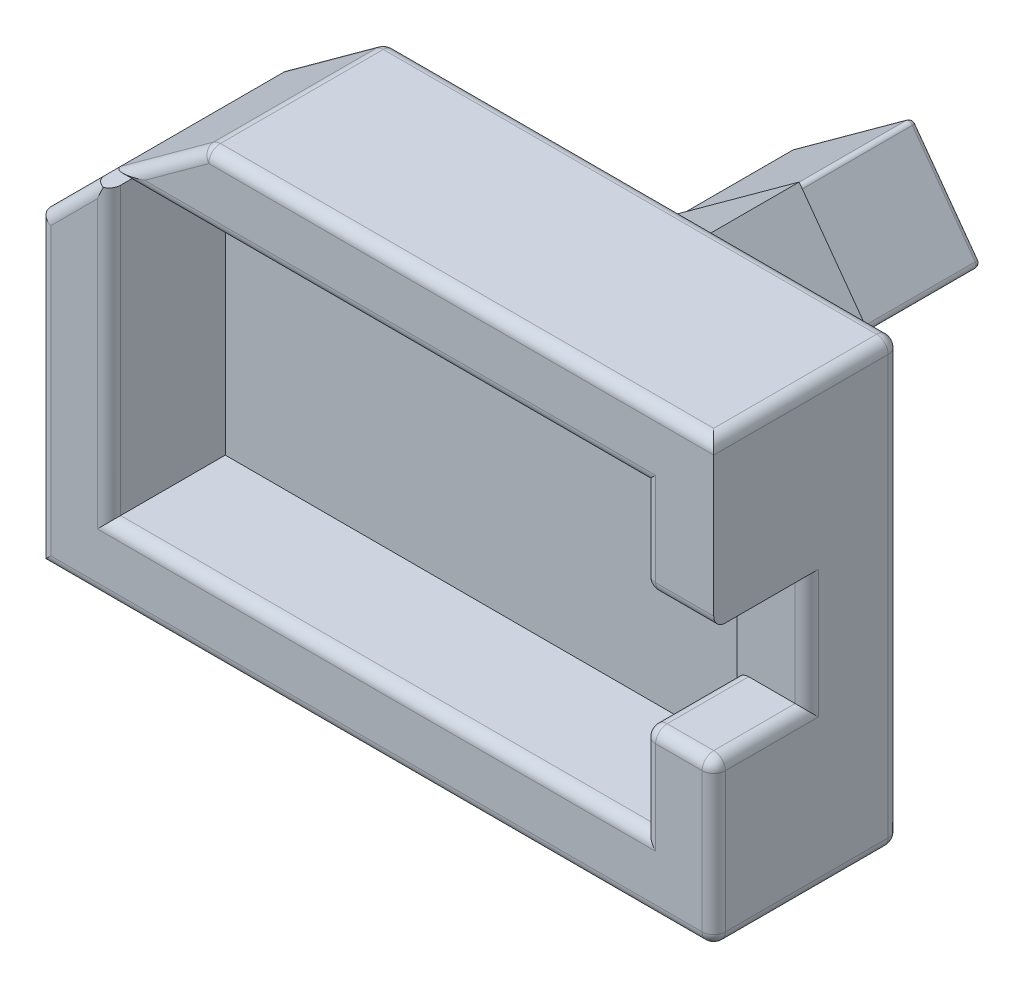
SolidWorks part; units mm, degrees
ref_plane "Front Plane" through (0, 0, 0) normal (0, 0, 1) x (1, 0, 0)
ref_plane "Top Plane" through (0, 0, 0) normal (0, 1, 0) x (1, 0, 0)
ref_plane "Right Plane" through (0, 0, 0) normal (1, 0, 0) x (0, 0, -1)
sketch "Sketch1" plane through (0, 0, 0) normal (0, 0, 1) x (1, 0, 0)
  line L0 (14.5, -9.5) -> (-14.5, -9.5)
  line L1 (11.5, -6.5) -> (-11.5, -6.5) construction
  line L2 (11.5, -6.5) -> (11.5, 6.5) construction
  line L3 (11.5, 6.5) -> (-11.5, 6.5) construction
  line L4 (-11.5, -6.5) -> (-11.5, 6.5) construction
  line L5 (11.5, -6.5) -> (-11.5, 6.5) construction
  line L6 (11.5, 6.5) -> (-11.5, -6.5) construction
  line L13 (14.5, -9.5) -> (14.5, 9.5) construction
  line L14 (14.5, -9.5) -> (-14.5, -9.5) construction
  line L17 (14.5, 9.5) -> (14.5, -9.5)
  line L19 (14.5, 9.5) -> (-14.5, 9.5) construction
  line L20 (-14.5, -9.5) -> (-14.5, 9.5) construction
  line L21 (14.5, 9.5) -> (-7.3709, 9.5)
  line L23 (-11.5, 6.5) -> (-14.5, 3.5)
  line L24 (-14.5, 3.5) -> (-14.5, -9.5)
  line L25 (-11.5, 6.5) -> (-7.3709, 9.5)
  point P0 (0, 0)
  dimension "D1" = 13
  dimension "D2" = 23
  dimension "D4" = 45
  dimension "D5" = 36
  dimension "D6" = 3
  dimension "D7" = 3
  dimension "D3" = 3
extrude "Boss-Extrude1" add sketch "Sketch1" along normal blind 3
sketch "Sketch2" plane through (0, 0, 3) normal (0, 0, 1) x (1, 0, 0)
  line L1 (11.5, -6.5) -> (-11.5, -6.5)
  line L3 (11.5, 6.5) -> (-11.5, 6.5)
  line L5 (11.5, -6.5) -> (-11.5, 6.5) construction
  line L6 (11.5, 6.5) -> (-11.5, -6.5) construction
  line L11 (14.5, -9.5) -> (-14.5, 9.5) construction
  line L12 (14.5, 9.5) -> (-14.5, -9.5) construction
  line L15 (7.3709, -9.5) -> (7.3709, 9.5) construction
  line L17 (-14.5, -9.5) -> (14.5, -9.5) construction
  line L18 (-14.5, -9.5) -> (14.5, -9.5)
  line L19 (14.5, -9.5) -> (14.5, 9.5)
  line L20 (14.5, -9.5) -> (14.5, 9.5) construction
  line L23 (11.5, -6.5) -> (11.5, 6.5)
  line L29 (14.5, -9.5) -> (14.5, 9.5) construction
  line L30 (14.5, 9.5) -> (-7.3709, 9.5)
  line L31 (14.5, 9.5) -> (-7.3709, 9.5) construction
  line L32 (-11.5, -6.5) -> (-11.5, 5.8)
  line L33 (-11.5, 6.5) -> (-7.3709, 9.5)
  line L34 (-11.5, 5.8) -> (-12.2, 5.8)
  line L35 (-11.5, 6.5) -> (-14.5, 3.5) construction
  line L36 (-12.2, 5.8) -> (-14.5, 3.5)
  line L37 (-14.5, 3.5) -> (-14.5, -9.5)
  point P0 (0, 0)
  point P7 (0, 0)
  dimension "D1" = 12.3
extrude "Boss-Extrude2" add sketch "Sketch2" along normal blind 5
sketch "Sketch3" plane through (0, 0, 0) normal (0, 0, -1) x (-1, 0, 0)
  line L0 (0, 0) -> (7.0906, 0) construction
  line L1 (4.0583, 0.1416) -> (1.1194, -3.9035)
  line L2 (4.0583, 0.1416) -> (-1.1194, 3.9035)
  line L3 (-1.1194, 3.9035) -> (-4.0583, -0.1416)
  line L4 (1.1194, -3.9035) -> (-4.0583, -0.1416)
  line L5 (4.0583, 0.1416) -> (-4.0583, -0.1416) construction
  line L6 (-1.1194, 3.9035) -> (1.1194, -3.9035) construction
  line L7 (0, 0) -> (-3.0495, -4.1972) construction
  line L8 (-1.1709, 4.0027) -> (4.1686, 0.1233)
  line L9 (4.1686, 0.1233) -> (1.1709, -4.0027)
  line L10 (1.1709, -4.0027) -> (-4.1686, -0.1233)
  line L11 (-4.1686, -0.1233) -> (-1.1709, 4.0027)
  point P0 (0, 0)
  dimension "D1" = 126
  dimension "D2" = 6.4
  dimension "D3" = 5.188
  dimension "D4" = 5
  dimension "D5" = 5.1
  dimension "D6" = 2.55
  dimension "D7" = 6.6
  dimension "D8" = 3.3
sketch "Sketch4" plane through (14.5, 0, 0) normal (1, 0, 0) x (0, 0, -1)
  line L1 (-8, 2.5) -> (-8, -2.5)
  line L2 (-4, -2.5) -> (-8, -2.5)
  line L3 (-4, -2.5) -> (-4, 2.5)
  line L4 (-4, 2.5) -> (-8, 2.5)
  line L5 (-8, -9.5) -> (0, -9.5) construction
  line L6 (-8, -9.5) -> (-8, 9.5) construction
  dimension "D3" = 5
  dimension "D4" = 4
  dimension "D5" = 7
extrude "Cut-Extrude1" cut sketch "Sketch4" against normal blind 8
fillet "Fillet2" radius 0.5 27 edges at (0, -9.5, 0) (14.5, 0, 0) (14.5, -9.5, 4) (11.5, 2.5, 6) (13, 2.5, 8) (14.5, 0, 4) (14.5, -2.5, 6) (11.5, -2.5, 6) (13, -2.5, 8) (14.5, -6, 8) (0, -9.5, 8) (0, -6.5, 8) (11.5, -4.5, 8) (0, 6.5, 8) (11.5, 4.5, 8) (-9.4354, 8, 8) (-13.35, 4.65, 8) (-14.5, -3, 0) (14.5, 9.5, 4) (3.5646, 9.5, 0) (-7.3709, 9.5, 4) (-9.4354, 8, 0) (-13, 5, 0) (-11.85, 5.8, 3) (-14.5, -3, 8) (3.5646, 9.5, 8) (-11.5, -0.35, 8)
extrude "Boss-Extrude4" add sketch "Sketch3" along normal blind 14 contours L4 L1 L2 L3 region at (0, 0, 0)
extrude "Boss-Extrude5" add sketch "Sketch3<5>" along normal blind 9
sketch "Sketch3<5>" plane through (0, 0, 0) normal (0, 0, -1) x (-1, 0, 0) same geometry as "Sketch3"
fillet "Fillet3" radius 0.2 8 edges at (-4.0583, 0.1416, -11.5) (-2.5889, -1.8809, -14) (-1.4695, 2.0225, -14) (1.4695, -2.0225, -14) (2.5889, 1.8809, -14) (1.1194, 3.9035, -11.5) (-1.1194, -3.9035, -11.5) (4.0583, -0.1416, -11.5)
